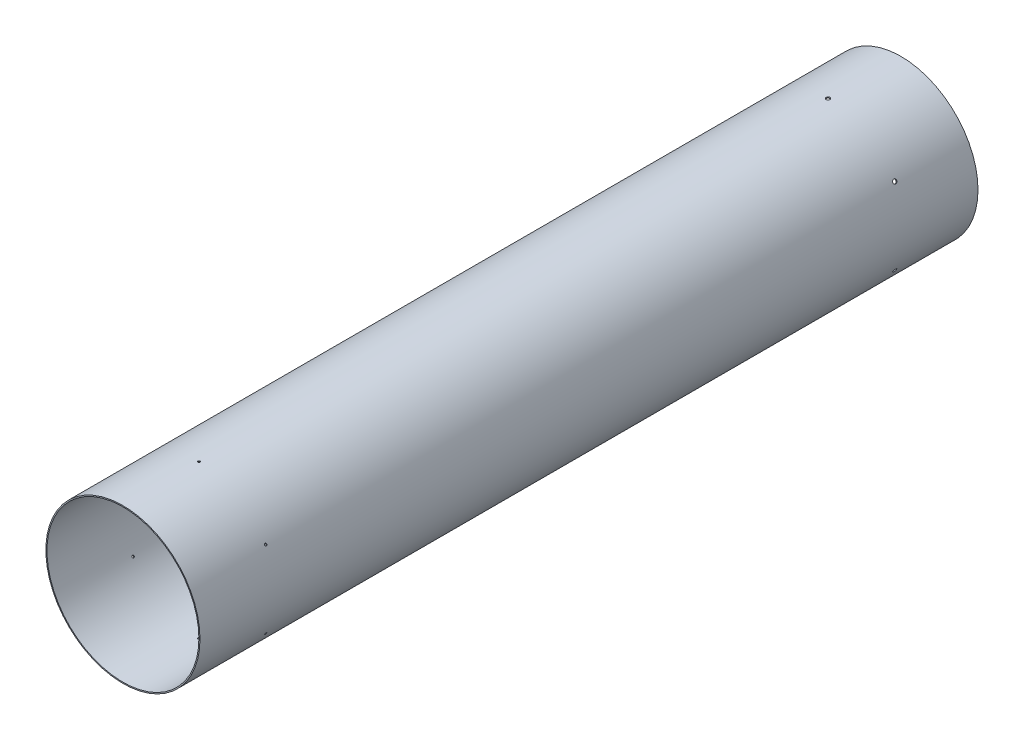
SolidWorks part; units mm, degrees
ref_plane "Front Plane" through (0, 0, 0) normal (0, 0, 1) x (1, 0, 0)
ref_plane "Top Plane" through (0, 0, 0) normal (0, 1, 0) x (1, 0, 0)
ref_plane "Right Plane" through (0, 0, 0) normal (1, 0, 0) x (0, 0, -1)
sketch "Sketch1" plane through (0, 0, 0) normal (0, 0, 1) x (1, 0, 0)
  circle A0 centre (0, 0) radius 79.375
  circle A1 centre (0, 0) radius 80.518
  dimension "D1" = 158.75
  dimension "D2" = 1.143
extrude "Boss-Extrude1" add sketch "Sketch1" along normal blind 812.8
ref_plane "Plane1" through (0, 80.518, 0) normal (0, 1, 0) x (1, 0, 0)
sketch "Sketch2" plane through (0, 80.518, 0) normal (0, 1, 0) x (1, 0, 0)
  line L0 (80.518, 0) -> (-80.518, 0) construction
  point P0 (0, -76.2)
  dimension "D1" = 76.2
hole_wizard "Tap Drill for #10-32 Tap1" positions "Sketch3" profile "Sketch4" hole size "#10-32" standard "ANSI Inch" end condition up to next
sketch "Sketch3" plane through (0, 80.518, 0) normal (0, 1, 0) x (1, 0, 0)
  point P0 (0, -76.2)
sketch "Sketch4" plane through (0, 80.518, 76.2) normal (1, 0, 0) x (0, 0, 1)
  line L0 (0, 0) -> (0, 1.143)
  line L1 (0, 1.143) -> (2.0193, 1.143)
  line L2 (2.0193, 1.143) -> (2.0193, 0)
  line L5 (2.0193, 0) -> (0, 0)
  line L11 (0, -6.35) -> (0, 107.95) construction
  dimension "Thru Hole Dia." = 4.0386
  dimension "Thru Hole Depth" = 1.143
sketch "Sketch5" plane through (0, 80.518, 0) normal (0, 1, 0) x (1, 0, 0)
  line L0 (-80.518, -812.8) -> (80.518, -812.8) construction
  point P0 (0, -733.425)
  dimension "D1" = 79.375
hole_wizard "Tap Drill for #4-40 Tap1" positions "Sketch6" profile "Sketch7" hole size "#4-40" standard "ANSI Inch" end condition up to next
sketch "Sketch6" plane through (0, 80.518, 0) normal (0, 1, 0) x (1, 0, 0)
  point P0 (0, -733.425)
sketch "Sketch7" plane through (0, 80.518, 733.425) normal (1, 0, 0) x (0, 0, 1)
  line L0 (0, 0) -> (0, 1.143)
  line L1 (0, 1.143) -> (1.1303, 1.143)
  line L2 (1.1303, 1.143) -> (1.1303, 0)
  line L5 (1.1303, 0) -> (0, 0)
  line L11 (0, -6.35) -> (0, 107.95) construction
  dimension "Thru Hole Dia." = 2.2606
  dimension "Thru Hole Depth" = 1.143
pattern_circular "CirPattern1" count 6 over 360 about axis through (0, 0, 812.8) along (0, 0, 1) of "Tap Drill for #10-32 Tap1", "Tap Drill for #4-40 Tap1"
